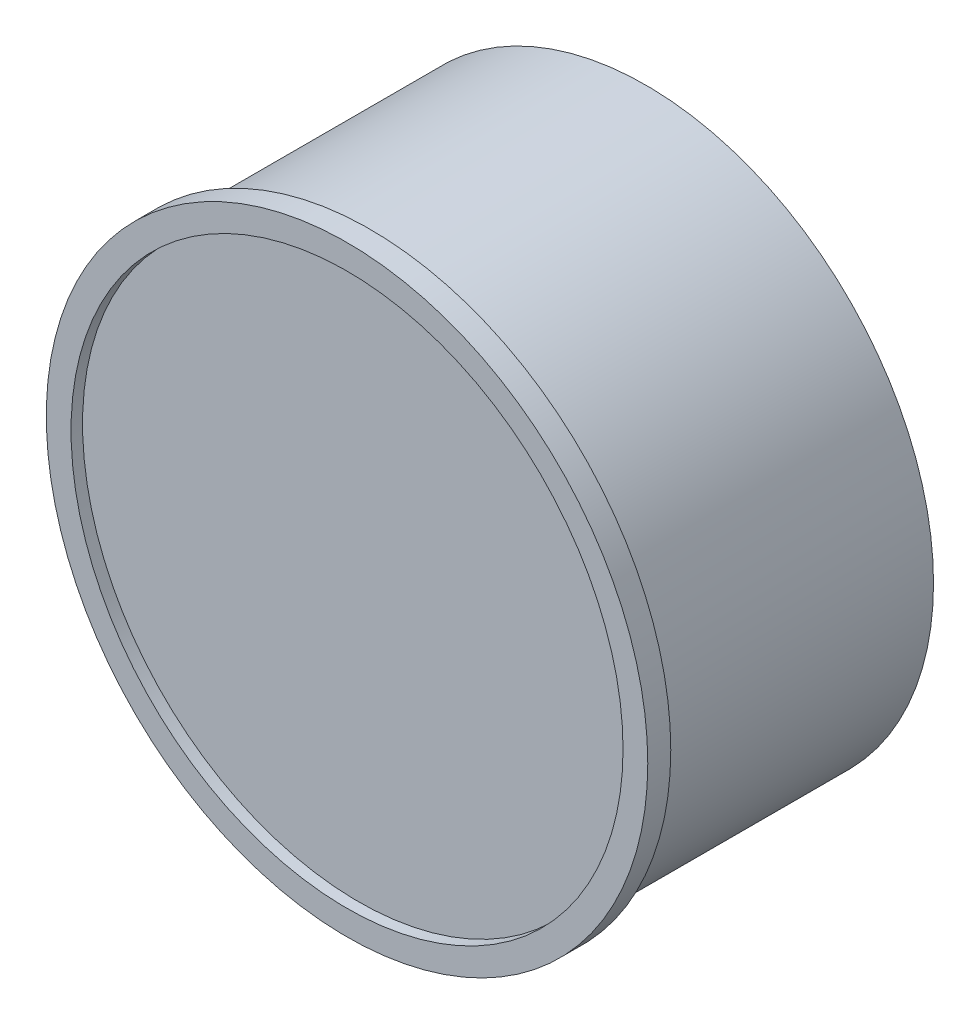
SolidWorks part; units mm, degrees
ref_plane "Front Plane" through (0, 0, 0) normal (0, 0, 1) x (1, 0, 0)
ref_plane "Top Plane" through (0, 0, 0) normal (0, 1, 0) x (1, 0, 0)
ref_plane "Right Plane" through (0, 0, 0) normal (1, 0, 0) x (0, 0, -1)
ref_axis "Axis X" through (-88.99, 0, 0) along (1, 0, 0)
ref_axis "Axis Y" through (0, 55, 0) along (0, -1, 0)
ref_axis "Axis Z" through (0, 0, -88.99) along (0, 0, 1)
sketch "Sketch1" plane through (0, 0, 0) normal (0, 0, 1) x (1, 0, 0)
  circle A0 centre (0, 0) radius 41.5163
  dimension "D1" = 83.0326
extrude "Boss-Extrude1" add sketch "Sketch1" along normal blind 3.175
sketch "Sketch2" plane through (0, 0, 0) normal (0, 0, -1) x (-1, 0, 0)
  circle A0 centre (0, 0) radius 39.6875
  dimension "D1" = 79.375
extrude "Boss-Extrude2" add sketch "Sketch2" along normal blind 38.1
sketch "Sketch3" plane through (0, 0, 3.175) normal (0, 0, 1) x (1, 0, 0)
  circle A0 centre (0, 0) radius 38.1
  dimension "D1" = 76.2
extrude "Cut-Extrude1" cut sketch "Sketch3" against normal blind 1.5875
